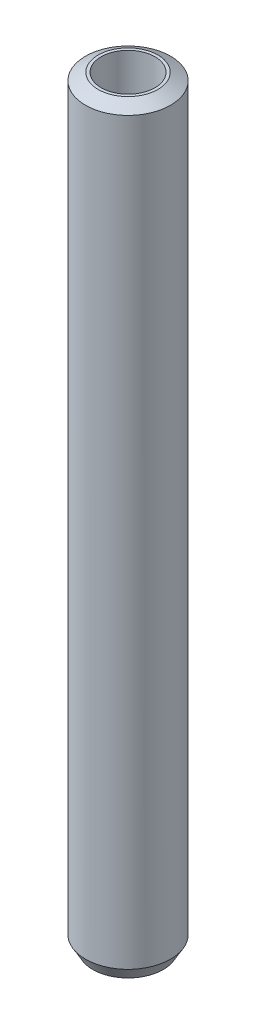
SolidWorks part; units mm, degrees
ref_plane "Front Plane" through (0, 0, 0) normal (0, 0, 1) x (1, 0, 0)
ref_plane "Top Plane" through (0, 0, 0) normal (0, 1, 0) x (1, 0, 0)
ref_plane "Right Plane" through (0, 0, 0) normal (1, 0, 0) x (0, 0, -1)
sketch "Sketch1" plane through (0, 0, 0) normal (0, 1, 0) x (1, 0, 0)
  circle A0 centre (0, 0) radius 25
  dimension "SHAFT_OD" = 50
extrude "Boss-Extrude1" add sketch "Sketch1" along normal blind 446.3814
sketch "Sketch2" plane through (0, 0, 0) normal (0, 1, 0) x (1, 0, 0)
  circle A0 centre (0, 0) radius 15.8136
  dimension "BORE_D" = 31.6273
extrude "Cut-Extrude1" cut sketch "Sketch2" along normal through all
chamfer "Chamfer1" distance 4.3018 angle 60 2 edges at (0, 446.3814, 25) (0, 0, 25) first distance on face at (0, 446.3814, 25) first distance on face at (0, 0, 15.8136)
